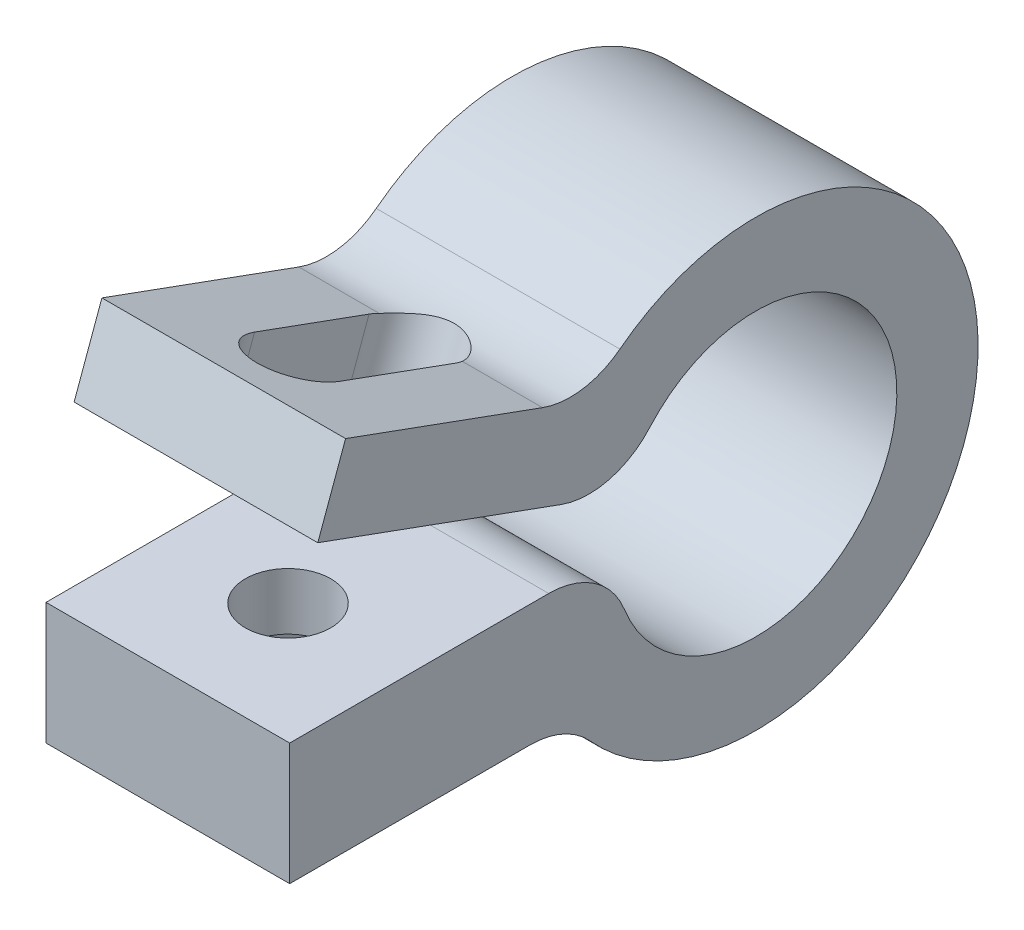
SolidWorks part; units mm, degrees
material "6061-T6 (SS)"
ref_plane "Front Plane" through (0, 0, 0) normal (0, 0, 1) x (1, 0, 0)
ref_plane "Top Plane" through (0, 0, 0) normal (0, 1, 0) x (1, 0, 0)
ref_plane "Right Plane" through (0, 0, 0) normal (1, 0, 0) x (0, 0, -1)
sketch "Sketch1" plane through (0, 0, 0) normal (1, 0, 0) x (0, 0, -1)
  line L0 (-11.475, 0) -> (-5.0966, 0)
  line L1 (-4.7893, 1.7431) -> (-10.783, 3.9247)
  line L4 (-5.2499, 4.0391) -> (-10.0989, 5.8041)
  line L5 (-11.475, 0) -> (-11.475, -2)
  line L6 (-10.783, 3.9247) -> (-10.0989, 5.8041)
  line L7 (-11.475, 0) -> (-3.475, 0) construction
  line L8 (-3.2654, 1.1885) -> (-10.783, 3.9247) construction
  line L9 (-11.475, -2) -> (-11.475, -3)
  line L10 (-11.475, -3) -> (-5.5566, -3)
  line L11 (-4.1052, 3.6225) -> (-10.0989, 5.8041) construction
  line L12 (-11.475, -2) -> (-5.0966, -2) construction
  arc A0 (-3.2348, -1.2694) -> (-2.6056, 2.2992) centre (0, 0) ccw
  arc A1 (-5.0966, -2) -> (-4.1052, 3.6225) centre (0, 0) ccw construction
  arc A2 (-4.0699, -3.6622) -> (-3.3442, 4.335) centre (0, 0) ccw
  arc A3 (-3.475, 0) -> (-3.2654, 1.1885) centre (0, 0) ccw construction
  arc A4 (-5.0966, 0) -> (-3.2348, -1.2694) centre (-5.0966, -2) cw
  arc A5 (-2.6056, 2.2992) -> (-4.7893, 1.7431) centre (-4.1052, 3.6225) cw
  circle A6 centre (0, 0) radius 3.175 construction
  arc A7 (-5.5566, -3) -> (-4.0699, -3.6622) centre (-5.5566, -5) cw
  arc A8 (-3.3442, 4.335) -> (-5.2499, 4.0391) centre (-4.5658, 5.9185) cw
  dimension "D1" = 0.3
  dimension "D5" = 2
  dimension "D6" = 6.35
  dimension "D7" = 1
  dimension "D8" = 2
  dimension "D2" = 6.3784
  dimension "D3" = 20
  dimension "D4" = 2
extrude "Boss-Extrude1" add sketch "Sketch1" along normal blind 6 separate body
sketch "Sketch3" plane through (0, 1.8794, -0.684) normal (0, 0.9397, -0.342) x (1, 0, 0)
  line L0 (0, -4.6252) -> (6, -11.475) construction
  line L1 (3, -6.5501) -> (3, -9.5501) construction
  line L2 (4.05, -6.5501) -> (4.05, -9.5501)
  line L3 (1.95, -6.5501) -> (1.95, -9.5501)
  arc A0 (4.05, -6.5501) -> (1.95, -6.5501) centre (3, -6.5501) ccw
  arc A1 (1.95, -9.5501) -> (4.05, -9.5501) centre (3, -9.5501) ccw
  point P6 (3, -8.0501)
  dimension "D1" = 1.05
  dimension "D2" = 3
extrude "Cut-Extrude1" cut sketch "Sketch3" against normal blind 2 and the other way blind 10
sketch "Sketch4" plane through (0, -3, 0) normal (0, -1, 0) x (1, 0, 0)
  line L0 (0, 11.475) -> (6, 5.5566) construction
  line L2 (4.1547, 10.5158) -> (1.8453, 10.5158)
  line L3 (1.8453, 10.5158) -> (0.6906, 8.5158)
  line L4 (0.6906, 8.5158) -> (1.8453, 6.5158)
  line L5 (1.8453, 6.5158) -> (4.1547, 6.5158)
  line L6 (4.1547, 6.5158) -> (5.3094, 8.5158)
  line L7 (5.3094, 8.5158) -> (4.1547, 10.5158)
  circle A0 centre (3, 8.5158) radius 1.05
  circle A1 centre (3, 8.5158) radius 2 construction
  dimension "D2" = 2.1
  dimension "D1" = 4
extrude "Cut-Extrude2" cut sketch "Sketch4" against normal blind 1.6
extrude "Cut-Extrude3" cut sketch "Sketch4<2>" against normal blind 4 contours A0 region at (3, -3, 8.5158)
sketch "Sketch4<2>" plane through (0, -3, 0) normal (0, -1, 0) x (1, 0, 0) same geometry as "Sketch4"
sketch "Sketch5" [suppressed] plane through (6, 0, 0) normal (1, 0, 0) x (0, 0, -1)
  line L0 (2.8861, 426.5135) -> (12.198, 432.2899)
  line L1 (12.198, 432.2899) -> (10.0249, 435.7931)
  line L2 (10.0249, 435.7931) -> (5.2213, 432.8133)
  arc A0 (-5.0966, 429.166) -> (-4.1052, 434.7885) centre (0, 431.166) ccw construction
  arc A1 (2.8861, 426.5135) -> (5.2213, 432.8133) centre (0, 431.166) ccw
extrude "Boss-Extrude2" [suppressed] add sketch "Sketch5" against normal up to surface (6 mm away)
ref_plane "Plane1" through (0, 1.9623, 11.129) normal (0, -0.1736, -0.9848) x (-1, 0, 0)
ref_point "Point2"
